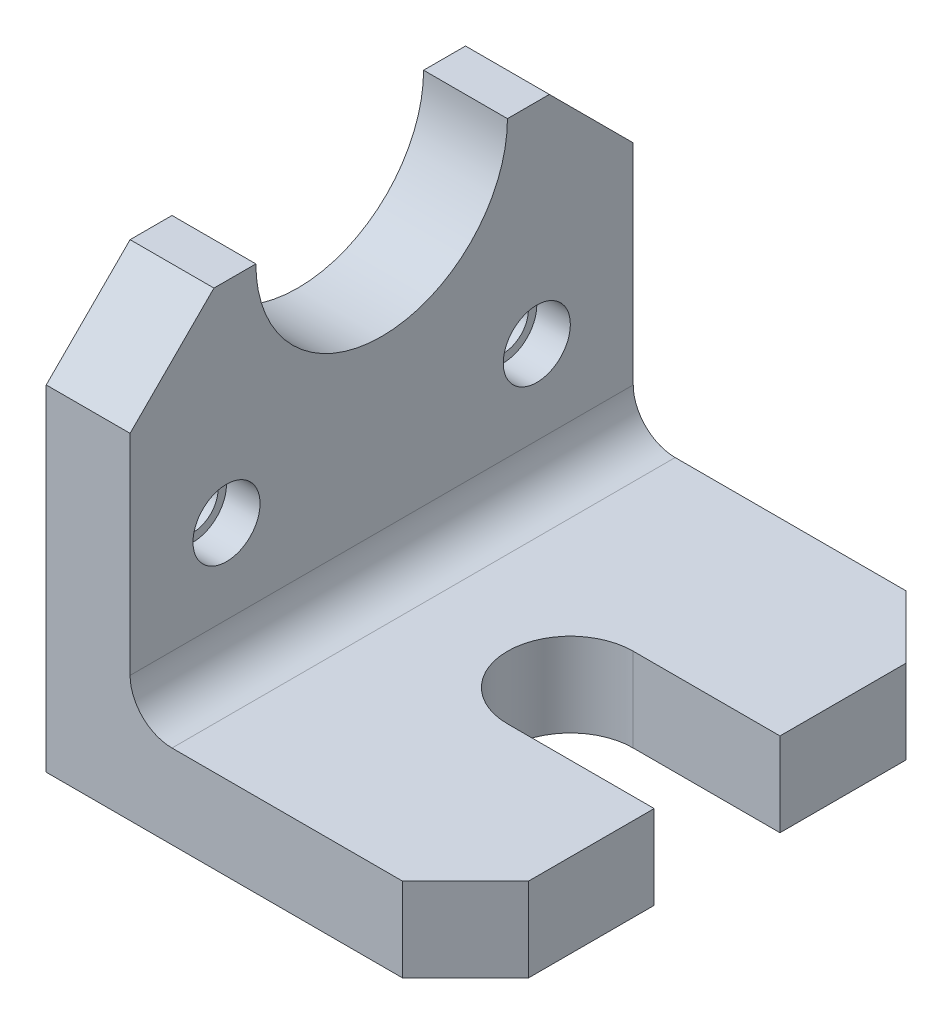
SolidWorks part; units mm, degrees
ref_plane "Front Plane" through (0, 0, 0) normal (0, 0, 1) x (1, 0, 0)
ref_plane "Top Plane" through (0, 0, 0) normal (0, 1, 0) x (1, 0, 0)
ref_plane "Right Plane" through (0, 0, 0) normal (1, 0, 0) x (0, 0, -1)
sketch "Sketch1" plane through (0, 0, 0) normal (0, 0, 1) x (1, 0, 0)
  line L0 (0, 0) -> (100, 0)
  line L1 (100, 0) -> (100, 20)
  line L2 (100, 20) -> (20, 20)
  line L3 (20, 20) -> (20, 100)
  line L4 (20, 100) -> (0, 100)
  line L5 (0, 100) -> (0, 0)
  dimension "D1" = 100
  dimension "D2" = 100
  dimension "D3" = 20
  dimension "D4" = 20
extrude "Boss-Extrude1" add sketch "Sketch1" along normal mid plane 120
chamfer "Chamfer1" distance 15 angle 45 2 edges at (100, 10, 60) (100, 10, -60)
chamfer "Chamfer2" distance 20 angle 45 2 edges at (10, 100, 60) (10, 100, -60)
fillet "Fillet2" radius 10 1 edges at (20, 20, 0)
sketch "Sketch2" plane through (20, 0, 0) normal (1, 0, 0) x (0, 0, -1)
  line L0 (60, 20) -> (-60, 20) construction
  line L1 (60, 30) -> (60, 80) construction
  line L2 (-40, 100) -> (40, 100) construction
  line L3 (-60, 30) -> (-60, 80) construction
  line L4 (-45, 0) -> (45, 0) construction
  circle A0 centre (-37, 50) radius 6
  circle A1 centre (-37, 50) radius 8
  circle A2 centre (37, 50) radius 6
  circle A3 centre (37, 50) radius 8
  arc A4 (-30, 100) -> (30, 100) centre (0, 100) ccw
  line M5 (40, 100) -> (-40, 100)
  dimension "D1" = 16
  dimension "D2" = 12
  dimension "D5" = 74
  dimension "D6" = 30
  dimension "D8" = 100
  dimension "D3" = 30
  dimension "D4" = 23
  dimension "D7" = 60
extrude "Cut-Extrude1" cut sketch "Sketch2" against normal up to next contours A4 M5 | A2 | A0 region at (20, 50, 37) region at (20, 50, -37) region at (20, 87.2676, 0)
extrude "Cut-Extrude2" cut sketch "Sketch2<3>" against normal blind 8 contours A3 A2 | A1 A0 region at (20, 50, 44.7737) region at (20, 50, -29.2263)
sketch "Sketch2<3>" plane through (20, 0, 0) normal (1, 0, 0) x (0, 0, -1) same geometry as "Sketch2"
sketch "Sketch3" plane through (0, 20, 0) normal (0, 1, 0) x (1, 0, 0)
  line L0 (100, 15) -> (65, 15)
  line L1 (100, -45) -> (100, 45) construction
  line L2 (65, -15) -> (100, -15)
  line L3 (85, -60) -> (30, -60) construction
  arc A0 (65, 15) -> (65, -15) centre (65, 0) ccw
  dimension "D1" = 30
  dimension "D3" = 15
  dimension "D2" = 45
  dimension "D4" = 35
extrude "Cut-Extrude3" cut sketch "Sketch3" against normal blind 20 and the other way through all
